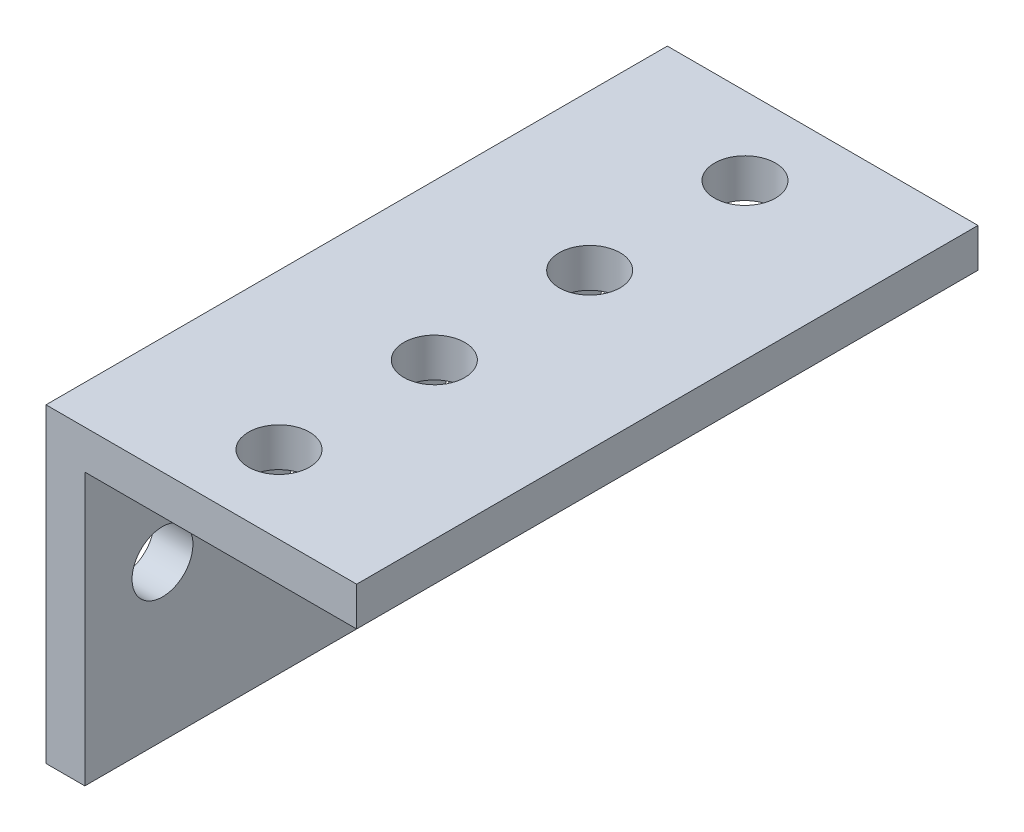
SolidWorks part; units mm, degrees
ref_plane "Front Plane" through (0, 0, 0) normal (0, 0, 1) x (1, 0, 0)
ref_plane "Top Plane" through (0, 0, 0) normal (0, 1, 0) x (1, 0, 0)
ref_plane "Right Plane" through (0, 0, 0) normal (1, 0, 0) x (0, 0, -1)
sketch "Sketch2" plane through (0, 0, 0) normal (0, 0, 1) x (1, 0, 0)
  line L0 (0, 0) -> (0, -25.4)
  line L1 (0, -25.4) -> (3.175, -25.4)
  line L2 (3.175, -25.4) -> (3.175, -3.175)
  line L3 (3.175, -3.175) -> (25.4, -3.175)
  line L4 (25.4, -3.175) -> (25.4, 0)
  line L5 (25.4, 0) -> (0, 0)
  dimension "D1" = 3.175
  dimension "D2" = 25.4
  dimension "D3" = 25.4
extrude "Boss-Extrude1" add sketch "Sketch2" along normal blind 50.8
sketch "Sketch5" plane through (3.175, 0, 0) normal (1, 0, 0) x (0, 0, -1)
  line L0 (-50.8, -25.4) -> (0, -25.4) construction
  line L1 (0, -25.4) -> (0, -3.175) construction
  circle A1 centre (-6.35, -12.7) radius 2.4892
  circle A2 centre (-19.05, -12.7) radius 2.4892
  circle A3 centre (-31.75, -12.7) radius 2.4892
  circle A4 centre (-44.45, -12.7) radius 2.4892
  dimension "D1" = 4.9784
  dimension "D2" = 12.7
  dimension "D3" = 6.35
  dimension "D4" = 4
  dimension "D5" = 12.7
extrude "Cut-Extrude1" cut sketch "Sketch5" against normal through all
sketch "Sketch6" plane through (0, -3.175, 0) normal (0, -1, 0) x (1, 0, 0)
  line L0 (3.175, 0) -> (25.4, 0) construction
  line L1 (25.4, 50.8) -> (25.4, 0) construction
  circle A0 centre (12.7, 6.35) radius 2.4892
  circle A1 centre (12.7, 19.05) radius 2.4892
  circle A2 centre (12.7, 31.75) radius 2.4892
  circle A3 centre (12.7, 44.45) radius 2.4892
  dimension "D3" = 4.9784
  dimension "D1" = 6.35
  dimension "D2" = 12.7
  dimension "D5" = 12.7
  dimension "D4" = 4
extrude "Cut-Extrude2" cut sketch "Sketch6" against normal through all
